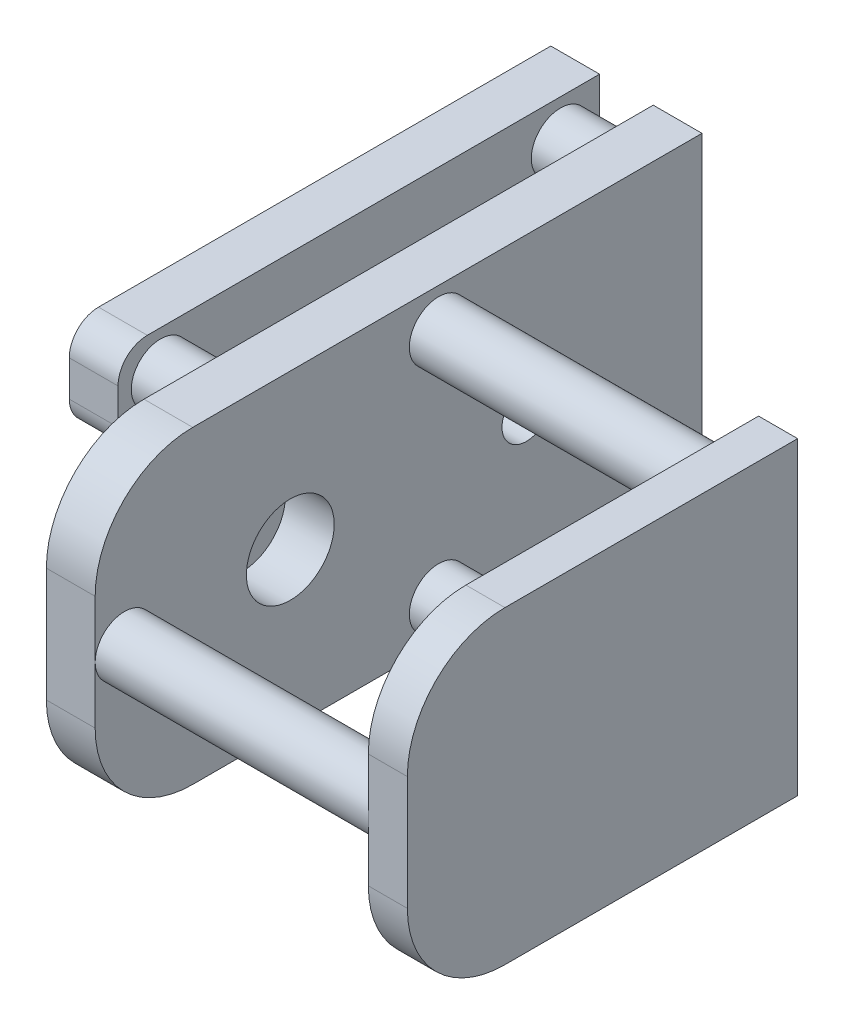
SolidWorks part; units mm, degrees
ref_plane "前视基准面" through (0, 0, 0) normal (0, 0, 1) x (1, 0, 0)
ref_plane "上视基准面" through (0, 0, 0) normal (0, 1, 0) x (1, 0, 0)
ref_plane "右视基准面" through (0, 0, 0) normal (1, 0, 0) x (0, 0, -1)
sketch "草图1" plane through (0, 0, 0) normal (1, 0, 0) x (0, 0, -1)
  line L1 (31.1, -15.85) -> (-21.1, -15.85)
  line L2 (31.1, -15.85) -> (31.1, 15.85)
  line L3 (31.1, 15.85) -> (-21.1, 15.85)
  line L4 (-31.1, -5.85) -> (-31.1, 5.85)
  line L5 (31.1, -15.85) -> (-31.1, 15.85) construction
  line L6 (31.1, 15.85) -> (-31.1, -15.85) construction
  circle A0 centre (-11.1, 0) radius 4.5
  circle A1 centre (13.1, 0) radius 2.5
  arc A2 (-31.1, -5.85) -> (-21.1, -15.85) centre (-21.1, -5.85) ccw
  arc A3 (-21.1, 15.85) -> (-31.1, 5.85) centre (-21.1, 5.85) ccw
  point P0 (0, 0)
  dimension "D3" = 9
  dimension "D6" = 5
  dimension "D7" = 10
  dimension "D1" = 31.7
  dimension "D2" = 62.2
  dimension "D4" = 20
  dimension "D5" = 18
extrude "凸台-拉伸1" add sketch "草图1" along normal blind 5
sketch "草图2" plane through (5, 0, 0) normal (1, 0, 0) x (0, 0, -1)
  line L0 (-31.1, 5.85) -> (-31.1, -5.85) construction
  line L1 (31.1, 15.85) -> (-21.1, 15.85) construction
  line L2 (-21.1, -15.85) -> (31.1, -15.85) construction
  line L3 (31.1, -15.85) -> (31.1, 15.85) construction
  circle A0 centre (-28.1, 0) radius 3
  circle A1 centre (4.1, 11.85) radius 3
  circle A2 centre (4.1, -11.85) radius 3
  dimension "D1" = 6
  dimension "D2" = 6
  dimension "D3" = 6
  dimension "D4" = 3
  dimension "D5" = 4
  dimension "D6" = 4
  dimension "D7" = 27
  dimension "D8" = 27
extrude "凸台-拉伸2" add sketch "草图2" along normal blind 28
sketch "草图3" plane through (33, 0, 0) normal (1, 0, 0) x (0, 0, -1)
  line L0 (31.1, 15.85) -> (-21.1, 15.85) construction
  line L1 (-21.1, -15.85) -> (31.1, -15.85) construction
  line L2 (-31.1, 0) -> (-31.1, -5.85) construction
  line L3 (-31.1, 5.85) -> (-31.1, 0) construction
  line L4 (8.9, 15.85) -> (-21.1, 15.85)
  line L5 (-21.1, -15.85) -> (8.9, -15.85)
  line L6 (-31.1, 0) -> (-31.1, -5.85)
  line L7 (-31.1, 5.85) -> (-31.1, 0)
  line L8 (8.9, 15.85) -> (8.9, -15.85)
  arc A0 (-31.1, -5.85) -> (-21.1, -15.85) centre (-21.1, -5.85) ccw construction
  arc A1 (-21.1, 15.85) -> (-31.1, 5.85) centre (-21.1, 5.85) ccw construction
  arc A2 (-31.1, -5.85) -> (-21.1, -15.85) centre (-21.1, -5.85) ccw
  arc A3 (-21.1, 15.85) -> (-31.1, 5.85) centre (-21.1, 5.85) ccw
  dimension "D1" = 40
extrude "凸台-拉伸3" add sketch "草图3" along normal blind 4
sketch "草图5" plane through (0, 0, 0) normal (-1, 0, 0) x (0, 0, 1)
  line L0 (-31.1, -15.85) -> (-31.1, 15.85) construction
  line L1 (-31.1, 15.85) -> (21.1, 15.85) construction
  circle A0 centre (-27.1, 11.85) radius 3
  circle A1 centre (-27.1, -11.9781) radius 3
  circle A2 centre (13.9, 11.85) radius 3
  circle A3 centre (13.9, -11.9781) radius 3
  dimension "D1" = 4
  dimension "D3" = 45
  dimension "D2" = 4
  dimension "D4" = 45
extrude "凸台-拉伸4" add sketch "草图5" along normal blind 5.5
sketch "草图6" plane through (-5.5, 0, 0) normal (-1, 0, 0) x (0, 0, 1)
  line L0 (21.1, -15.85) -> (-31.1, -15.85) construction
  line L1 (-31.1, -15.85) -> (-31.1, 15.85) construction
  line L2 (-31.1, 15.85) -> (21.1, 15.85) construction
  line L3 (15.2557, -15.85) -> (-31.1, -15.85)
  line L4 (-31.1, -15.85) -> (-31.1, 15.85)
  line L5 (-31.1, 15.85) -> (15.2557, 15.85)
  line L6 (18.2557, 12.85) -> (18.2557, 9.1837)
  line L7 (15.2557, 6.1837) -> (8.6961, 6.1837)
  line L8 (5.6961, 3.1837) -> (5.6961, -3.1837)
  line L9 (8.6961, -6.1837) -> (15.2557, -6.1837)
  line L10 (18.2557, -9.1837) -> (18.2557, -12.85)
  arc A0 (15.2557, -15.85) -> (18.2557, -12.85) centre (15.2557, -12.85) ccw
  arc A3 (18.2557, 12.85) -> (15.2557, 15.85) centre (15.2557, 12.85) ccw
  arc A4 (18.2557, -9.1837) -> (15.2557, -6.1837) centre (15.2557, -9.1837) ccw
  arc A5 (8.6961, -6.1837) -> (5.6961, -3.1837) centre (8.6961, -3.1837) cw
  arc A6 (8.6961, 6.1837) -> (5.6961, 3.1837) centre (8.6961, 3.1837) ccw
  arc A7 (18.2557, 9.1837) -> (15.2557, 6.1837) centre (15.2557, 9.1837) cw
  dimension "D2" = 3
extrude "凸台-拉伸6" add sketch "草图6" along normal blind 5
